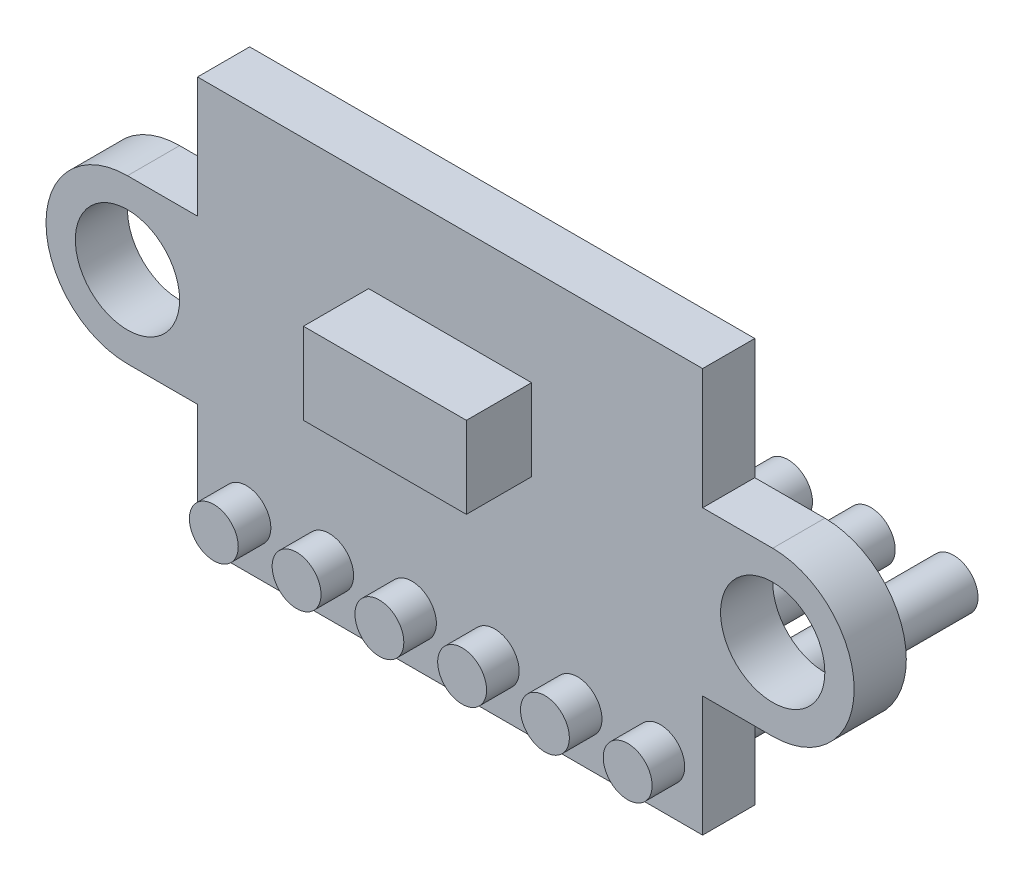
SolidWorks part; units mm, degrees
ref_plane "Front Plane" through (0, 0, 0) normal (0, 0, 1) x (1, 0, 0)
ref_plane "Top Plane" through (0, 0, 0) normal (0, 1, 0) x (1, 0, 0)
ref_plane "Right Plane" through (0, 0, 0) normal (1, 0, 0) x (0, 0, -1)
sketch "Sketch1" plane through (0, 0, 0) normal (0, 0, 1) x (1, 0, 0)
  line L0 (-7.75, 6.2) -> (7.75, 6.2)
  line L1 (7.75, 6.2) -> (7.75, 2.5)
  line L2 (7.75, 2.5) -> (9.9, 2.5)
  line L3 (9.9, -2.5) -> (7.75, -2.5)
  line L4 (7.75, -2.5) -> (7.75, -6.2)
  line L5 (7.75, -6.2) -> (-7.75, -6.2)
  line L6 (-7.75, -6.2) -> (-7.75, -2.5)
  line L7 (-7.75, -2.5) -> (-9.9, -2.5)
  line L8 (-7.75, 6.2) -> (-7.75, 2.5)
  line L9 (-7.75, 2.5) -> (-9.9, 2.5)
  line L10 (-9.9, 0) -> (9.9, 0) construction
  line L11 (-7.75, 6.2) -> (7.75, -6.2) construction
  arc A0 (9.9, 2.5) -> (9.9, -2.5) centre (9.9, 0) cw
  arc A1 (-9.9, 2.5) -> (-9.9, -2.5) centre (-9.9, 0) ccw
  circle A2 centre (-9.9, 0) radius 1.6
  circle A3 centre (9.9, 0) radius 1.6
  point P17 (-0.5364, 6.1018)
  point P21 (0, 0)
  dimension "D2" = 3.2
  dimension "D4" = 2.5
  dimension "D1" = 15.5
  dimension "D3" = 12.4
  dimension "D5" = 19.8
extrude "Main" add sketch "Sketch1" along normal blind 1.6
sketch "Sketch2" plane through (0, 0, 1.6) normal (0, 0, 1) x (1, 0, 0)
  line L0 (7.75, 6.2) -> (-7.75, 6.2) construction
  line L1 (-2.5, 3.2) -> (2.5, 3.2)
  line L2 (-2.5, 3.2) -> (-2.5, 0.7)
  line L3 (-2.5, 0.7) -> (2.5, 0.7)
  line L4 (2.5, 3.2) -> (2.5, 0.7)
  line L5 (-7.75, 6.2) -> (-7.75, 2.5) construction
  dimension "D1" = 5
  dimension "D2" = 3
  dimension "D3" = 2.5
  dimension "D4" = 5.25
extrude "Sensor" add sketch "Sketch2" along normal blind 2
ref_plane "Plane1" through (0, 0, 2.6) normal (0, 0, 1) x (1, 0, 0)
sketch "Sketch3" plane through (0, 0, 2.6) normal (0, 0, 1) x (1, 0, 0)
  line L0 (-7.75, -6.2) -> (7.75, -6.2) construction
  line L1 (-7.75, -2.5) -> (-7.75, -6.2) construction
  circle A0 centre (-6.25, -4.66) radius 0.75
  dimension "D3" = 1.5
  dimension "D1" = 1.54
  dimension "D2" = 1.5
extrude "Cables" add sketch "Sketch3" against normal blind 10
pattern_linear "LPattern1" count 6 spacing 2.54 along (1, 0, 0) of "Cables"
